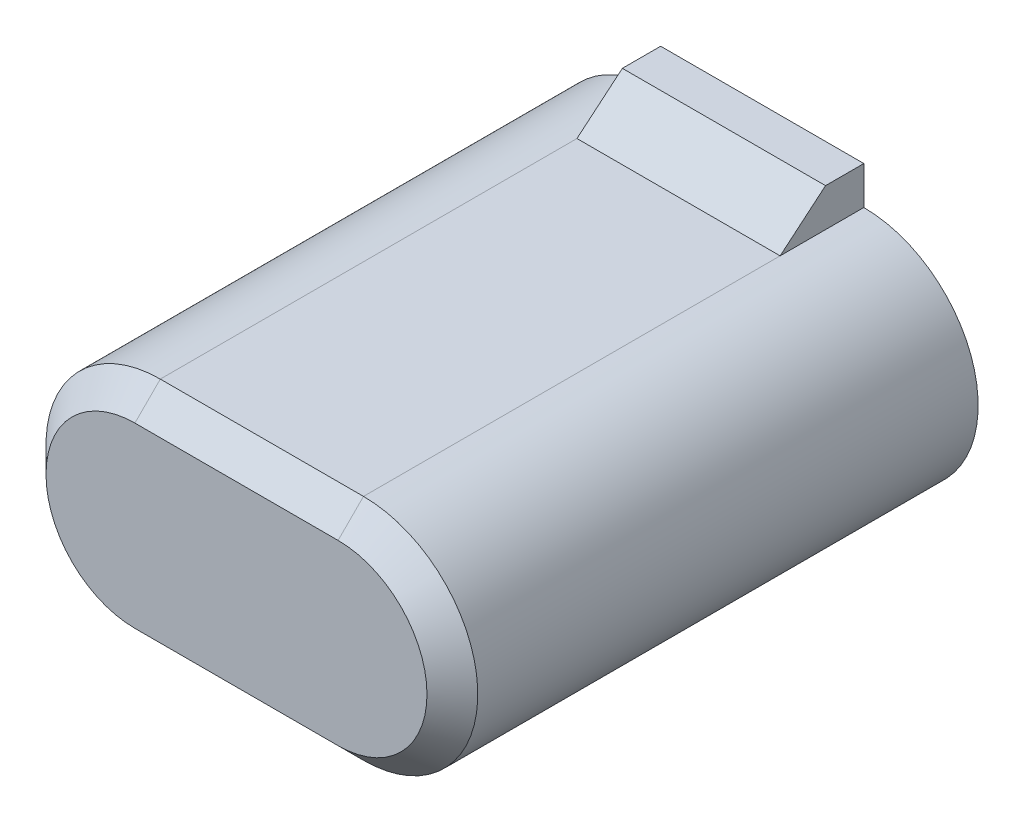
SolidWorks part; units mm, degrees
ref_plane "Front Plane" through (0, 0, 0) normal (0, 0, 1) x (1, 0, 0)
ref_plane "Top Plane" through (0, 0, 0) normal (0, 1, 0) x (1, 0, 0)
ref_plane "Right Plane" through (0, 0, 0) normal (1, 0, 0) x (0, 0, -1)
sketch "Sketch1" plane through (0, 0, 0) normal (0, 0, 1) x (1, 0, 0)
  line L0 (-2, 0) -> (2, 0) construction
  line L1 (-2, 2.5) -> (2, 2.5)
  line L2 (-2, -2.5) -> (2, -2.5)
  arc A0 (-2, 2.5) -> (-2, -2.5) centre (-2, 0) ccw
  arc A1 (2, -2.5) -> (2, 2.5) centre (2, 0) ccw
  point P2 (0, 0)
  dimension "D1" = 5
  dimension "D2" = 4
sketch "Sketch2" plane through (0, 0, 0) normal (0, 0, 1) x (1, 0, 0)
  line L0 (-2, 0) -> (2, 0) construction
  line L1 (-2, 2.25) -> (2, 2.25)
  line L2 (-2, -2.25) -> (2, -2.25)
  line L3 (-2, 2.5) -> (2, 2.5) construction
  arc A0 (-2, 2.25) -> (-2, -2.25) centre (-2, 0) ccw
  arc A1 (2, -2.25) -> (2, 2.25) centre (2, 0) ccw
  arc A2 (-2, 2.5) -> (-2, -2.5) centre (-2, 0) ccw construction
  point P2 (0, 0)
  dimension "D1" = 0.25
sketch "Sketch3" plane through (0, 0, 0) normal (1, 0, 0) x (0, 0, -1)
  line L0 (0, 0) -> (-10.35, 0)
  point P3 (-1.35, 0)
  dimension "D1" = 10.35
  dimension "D2" = 1.35
sketch "Sketch4" plane through (0, 0, 0) normal (1, 0, 0) x (0, 0, -1)
  line L0 (0, 0) -> (0.9315, 0.7816)
  line L1 (0, 2.5) -> (0, -2.5) construction
  line L2 (0, 0) -> (0.9315, -0.7816)
  line L3 (0, 0) -> (-10.35, 0) construction
  line L4 (0, 0) -> (2.5274, 0) construction
  dimension "D1" = 140
extrude "Boss-Extrude1" add sketch "Sketch2" along normal up to vertex (10.35 mm away) up to point (0, 0, 10.35)
sketch "Sketch5" plane through (0, 0, 0) normal (1, 0, 0) x (0, 0, -1)
  line L0 (-1.6479, 2.25) -> (-0.7541, 3)
  line L1 (-10.35, 2.25) -> (0, 2.25) construction
  line L2 (-0.7541, 3) -> (0, 3)
  line L3 (-1.35, 2.5) -> (0, 2.5) construction
  line L4 (-1.6479, 2.25) -> (0, 2.25)
  line L5 (0, 0) -> (3.6454, 0) construction
  line L6 (0, 3) -> (0, 2.25)
  line L7 (-1.6479, -2.25) -> (0, -2.25)
  line L8 (0, -3) -> (0, -2.25)
  line L9 (-0.7541, -3) -> (0, -3)
  line L10 (-1.6479, -2.25) -> (-0.7541, -3)
  line L12 (-1.35, 0) -> (-1.35, 2.5) construction
  dimension "D1" = 140
  dimension "D2" = 0.75
extrude "Boss-Extrude2" add sketch "Sketch5" along normal up to vertex (2 mm away) and the other way up to vertex (2 mm away) up to point (2, 2.25, 0) other way up to point (-2, 2.25, 0)
chamfer "Chamfer1" distance 0.5 angle 45 4 edges at (0, 2.25, 10.35) (-4.25, 0, 10.35) (4.25, 0, 10.35) (0, -2.25, 10.35)
ref_axis "Axis1" through (0, 0, 0) along (0, 0, 1)
